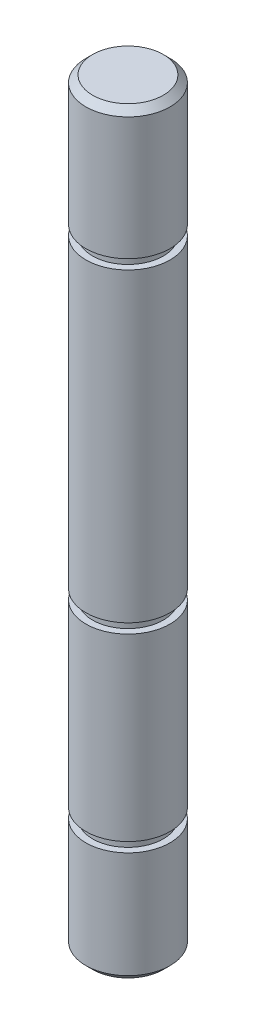
SolidWorks part; units mm, degrees
material "6061-T6 (SS)"
ref_plane "Front" through (0, 0, 0) normal (0, 0, 1) x (1, 0, 0)
ref_plane "Top" through (0, 0, 0) normal (0, 1, 0) x (1, 0, 0)
ref_plane "Right" through (0, 0, 0) normal (1, 0, 0) x (0, 0, -1)
ref_axis "side-side" through (80.9, 0, 0) along (-1, 0, 0)
ref_axis "up-down" through (0, 50, 0) along (0, -1, 0)
ref_axis "front-back" through (0, 0, -80.9) along (0, 0, 1)
sketch "Sketch1" plane through (0, 0, 0) normal (0, 0, 1) x (1, 0, 0)
  line L0 (0, 0) -> (0, -69.7999) construction
  line L1 (-3.175, 47.3738) -> (-3.175, 57.15)
  line L2 (0, 0) -> (-3.175, 0)
  line L3 (0, 0) -> (0, 57.15)
  line L4 (0, 57.15) -> (-3.175, 57.15)
  line L5 (-3.175, 0) -> (-3.175, 8.5372)
  line L6 (-3.175, 47.3738) -> (-2.667, 47.3738)
  line L7 (-3.175, 23.574) -> (-3.175, 46.6372)
  line L8 (-3.175, 46.6372) -> (-2.667, 46.6372)
  line L9 (-2.667, 47.3738) -> (-2.667, 46.6372)
  line L10 (-3.175, 23.574) -> (-2.667, 23.574)
  line L11 (4.1402, 22.5834) -> (-4.1402, 22.5834) construction
  line L12 (-3.175, 22.8374) -> (-2.667, 22.8374)
  line L13 (-2.667, 23.574) -> (-2.667, 22.8374)
  line L14 (-11.0871, 47.6278) -> (11.0871, 47.6278) construction
  line L15 (-16.5489, 10.239) -> (0, 10.239) construction
  line L16 (11.0871, 22.5834) -> (-11.0871, 22.5834) construction
  line L17 (-3.175, 8.5372) -> (-2.667, 8.5372)
  line L18 (-11.0871, 47.6278) -> (11.0871, 47.6278) construction
  line L19 (-3.175, 9.2738) -> (-2.667, 9.2738)
  line L20 (-2.667, 8.5372) -> (-2.667, 9.2738)
  line L21 (-3.175, 9.2738) -> (-3.175, 22.8374)
  point P14 (-1.5875, 57.15)
  dimension "D1" = 6.35
  dimension "D2" = 5.334
  dimension "D3" = 0.7366
  dimension "D4" = 57.15
  dimension "D5" = 9.7762
  dimension "D6" = 22.8374
  dimension "D7" = 0.254
  dimension "D8" = 0.254
  dimension "D9" = 0.9652
revolve "Revolve1" add sketch "Sketch1" angle 360 about L0
chamfer "Chamfer1" distance 0.508 angle 45 2 edges at (0, 0, 3.175) (0, 57.15, 3.175)
